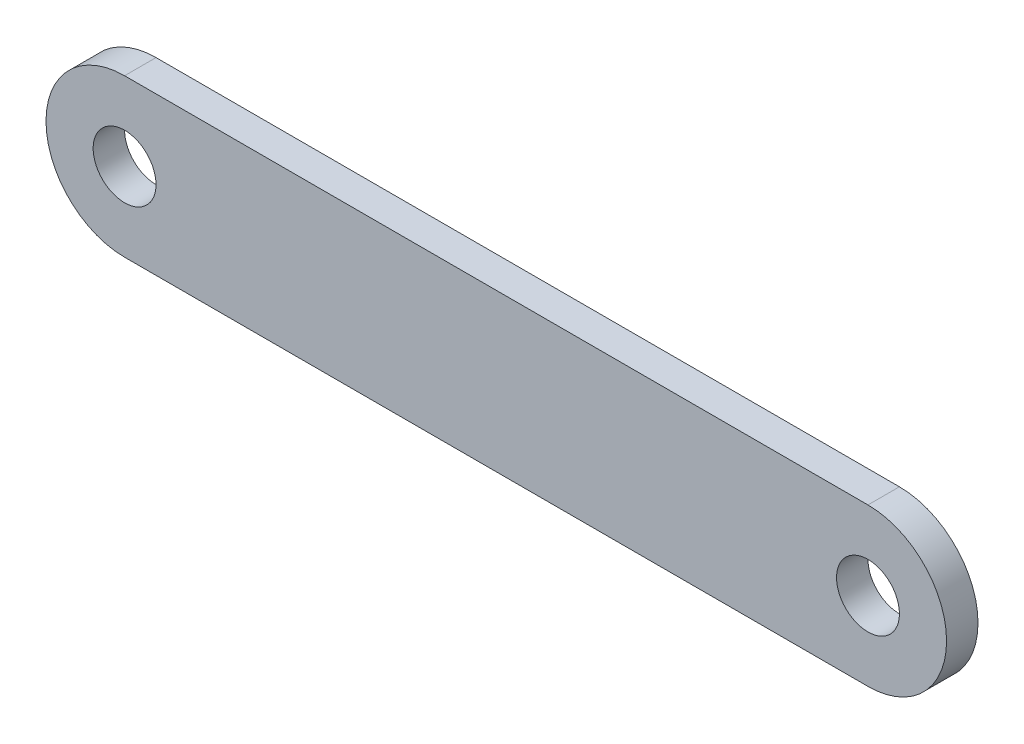
SolidWorks part; units mm, degrees
ref_plane "Front Plane" through (0, 0, 0) normal (0, 0, 1) x (1, 0, 0)
ref_plane "Top Plane" through (0, 0, 0) normal (0, 1, 0) x (1, 0, 0)
ref_plane "Right Plane" through (0, 0, 0) normal (1, 0, 0) x (0, 0, -1)
sketch "Sketch1" plane through (0, 0, 0) normal (0, 0, 1) x (1, 0, 0)
  line L0 (-59.1204, 0) -> (59.1204, 0) construction
  line L1 (-59.1204, 12.5) -> (59.1204, 12.5)
  line L2 (-59.1204, -12.5) -> (59.1204, -12.5)
  arc A0 (-59.1204, 12.5) -> (-59.1204, -12.5) centre (-59.1204, 0) ccw
  arc A1 (59.1204, -12.5) -> (59.1204, 12.5) centre (59.1204, 0) ccw
  point P2 (0, 0)
  dimension "D1" = 118.2407
  dimension "D3" = 25
extrude "Boss-Extrude1" add sketch "Sketch1" along normal blind 5
hole_wizard "M8 Clearance Hole1" positions "Sketch4" profile "Sketch5" hole size "M8" standard "ANSI Metric" end condition through all
sketch "Sketch4" plane through (0, 0, 5) normal (0, 0, 1) x (1, 0, 0)
  point P0 (-59.1204, 0)
  point P3 (59.1204, 0)
sketch "Sketch5" plane through (-59.1204, 0, 5) normal (1, 0, 0) x (0, -1, 0)
  line L0 (0, 0) -> (0, 5)
  line L1 (0, 5) -> (5, 5)
  line L2 (5, 5) -> (5, 0)
  line L5 (5, 0) -> (0, 0)
  line L11 (0, -6.35) -> (0, 107.95) construction
  dimension "Thru Hole Dia." = 10
  dimension "Thru Hole Depth" = 5
